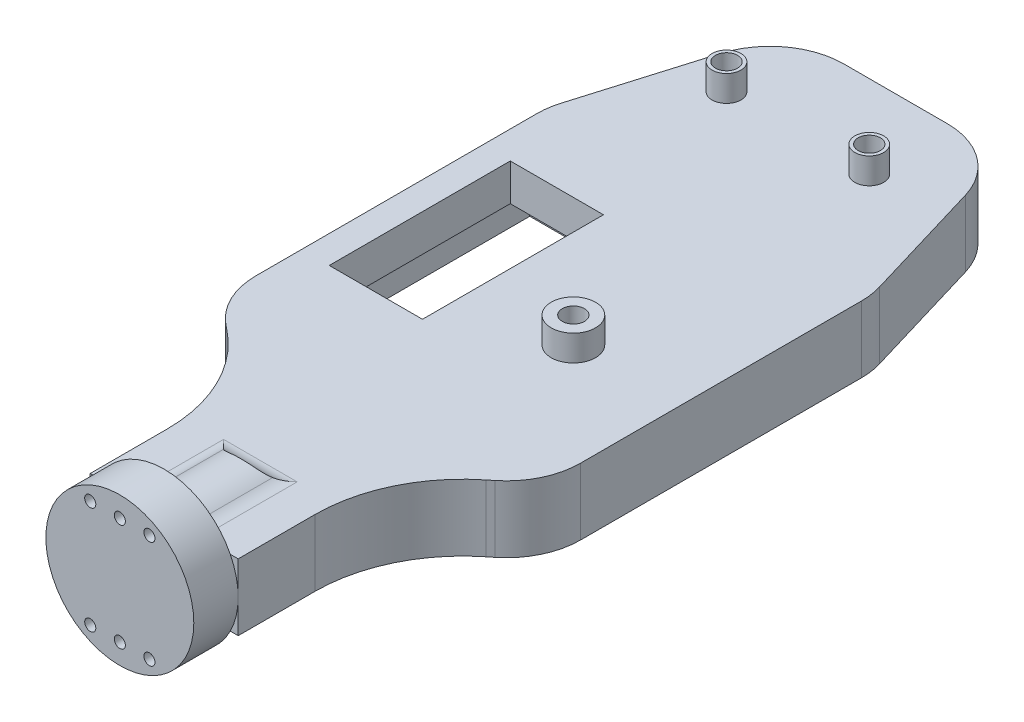
SolidWorks part; units mm, degrees
ref_plane "Front Plane" through (0, 0, 0) normal (0, 0, 1) x (1, 0, 0)
ref_plane "Top Plane" through (0, 0, 0) normal (0, 1, 0) x (1, 0, 0)
ref_plane "Right Plane" through (0, 0, 0) normal (1, 0, 0) x (0, 0, -1)
sketch "Sketch1" plane through (0, 0, 0) normal (0, 0, 1) x (1, 0, 0)
  circle A0 centre (0, 0) radius 10
  dimension "D1" = 20
extrude "Boss-Extrude1" add sketch "Sketch1" along normal blind 6 contours A0
sketch "Sketch2" plane through (0, 0, 6) normal (0, 0, 1) x (1, 0, 0)
  line L0 (0, 0) -> (15.637, 0) construction
  circle A0 centre (0, 7.25) radius 0.75
  circle A1 centre (4, 7.25) radius 0.75
  circle A2 centre (-4, 7.25) radius 0.75
  circle A3 centre (4, -7.25) radius 0.75
  circle A4 centre (0, -7.25) radius 0.75
  circle A5 centre (-4, -7.25) radius 0.75
  point P6 (0, 0)
  dimension "D3" = 1.5
  dimension "D1" = 7.25
  dimension "D2" = 4
  dimension "D4" = 4
extrude "Cut-Extrude1" cut sketch "Sketch2" against normal blind 15
sketch "Sketch4" plane through (0, 0, 0) normal (0, 0, -1) x (-1, 0, 0)
  circle A0 centre (0, 0) radius 6
  dimension "D1" = 12
extrude "Boss-Extrude3" add sketch "Sketch4" along normal blind 10
sketch "Sketch5" plane through (0, 0, 0) normal (0, 1, 0) x (1, 0, 0)
  line L0 (6, 0) -> (-6, 0) construction
  line L1 (-10, 20) -> (10, 20)
  line L2 (-10, 20) -> (-10, 0)
  line L3 (-10, 0) -> (10, 0)
  line L4 (10, 20) -> (10, 0)
  line L5 (-10, 20) -> (10, 0) construction
  line L6 (-10, 0) -> (10, 20) construction
  line L7 (10, 0) -> (-10, 0) construction
  point P0 (0, 10)
  dimension "D1" = 20
  dimension "D2" = 20
extrude "Boss-Extrude4" add sketch "Sketch5" against normal mid plane 9
sketch "Sketch6" plane through (0, 4.5, 0) normal (0, 1, 0) x (1, 0, 0)
  line L0 (10, 20) -> (35.7632, 40.5564)
  line L1 (-10, 20) -> (-35.7632, 40.5564)
  line L2 (-35.7632, 40.5564) -> (-35.7632, 98.8831)
  line L3 (-35.7632, 98.8831) -> (35.7632, 98.8831)
  line L4 (35.7632, 98.8831) -> (35.7632, 40.5564)
  line L15 (-3.9686, 0) -> (-3.9686, 10)
  line L16 (-3.9686, 10) -> (3.9686, 10)
  line L17 (3.9686, 10) -> (3.9686, 0)
  line L18 (3.9686, 0) -> (8.9303, 0)
  line L19 (8.9303, 0) -> (10, 0)
  line L20 (10, 0) -> (10, 20)
  line L21 (10, 20) -> (-10, 20)
  line L22 (-10, 20) -> (-10, 0)
  line L23 (-10, 0) -> (-8.9303, 0)
  line L24 (-8.9303, 0) -> (-3.9686, 0)
  line L31 (10, 20) -> (-10, 20)
  point P15 (0, 98.8831)
  dimension "D1" = 0
extrude "Boss-Extrude5" add sketch "Sketch6" against normal up to surface (9 mm away) up to face at (0, -4.5, -6)
sketch "Sketch7" plane through (0, -4.5, 0) normal (0, -1, 0) x (1, 0, 0)
  line L1 (-4.3923, -33.8071) -> (-19.3923, -33.8071)
  line L2 (-4.3923, -33.8071) -> (-4.3923, -68.8071)
  line L3 (-4.3923, -68.8071) -> (-19.3923, -68.8071)
  line L4 (-19.3923, -33.8071) -> (-19.3923, -68.8071)
  line L5 (-4.3923, -33.8071) -> (-19.3923, -68.8071) construction
  line L6 (-4.3923, -68.8071) -> (-19.3923, -33.8071) construction
  point P0 (-11.8923, -51.3071)
  dimension "D1" = 15
  dimension "D2" = 35
extrude "Cut-Extrude2" cut sketch "Sketch7" against normal blind 4
sketch "Sketch8" plane through (0, -0.5, 0) normal (0, -1, 0) x (1, 0, 0)
  line L0 (-11.8923, -33.8071) -> (-11.8923, -68.8071) construction
  line L1 (-4.3923, -33.8071) -> (-19.3923, -33.8071) construction
  line L2 (-19.3923, -68.8071) -> (-4.3923, -68.8071) construction
  line L3 (-18.1923, -55.7744) -> (-18.1923, -40.5057)
  line L4 (-18.1923, -40.5057) -> (-5.5923, -40.5057)
  line L5 (-5.5923, -40.5057) -> (-5.5923, -55.7744)
  line L6 (-18.1923, -55.7744) -> (-18.1923, -64.9741)
  line L7 (-18.1923, -64.9741) -> (-5.5923, -64.9741)
  line L8 (-5.5923, -64.9741) -> (-5.5923, -55.7744)
  point P0 (-11.8923, -40.5057)
extrude "Cut-Extrude3" cut sketch "Sketch8" against normal blind 14 contours L4 L5 L8 L7 L6 L3
sketch "Sketch10" plane through (0, -4.5, 0) normal (0, -1, 0) x (1, 0, 0)
  line L0 (-21.9398, -73.7699) -> (-14.4454, -98.8831)
  line L2 (-35.7632, -98.8831) -> (35.7632, -98.8831) construction
  line L5 (0, 0) -> (0, -94.3772) construction
  line L9 (-21.9398, -73.7699) -> (-21.9398, -29.5267)
  line L10 (-10, -20) -> (-35.7632, -40.5564) construction
  line L11 (-21.9398, -29.5267) -> (-35.7632, -40.5564)
  line L15 (-35.7632, -40.5564) -> (-35.7632, -98.8831)
  line L16 (-35.7632, -98.8831) -> (-14.4454, -98.8831)
  line L17 (35.7632, -40.5564) -> (35.7632, -98.8831)
  line L18 (21.9398, -29.5267) -> (35.7632, -40.5564)
  line L19 (21.9398, -73.7699) -> (21.9398, -29.5267)
  line L20 (21.9398, -73.7699) -> (14.4454, -98.8831)
  line L21 (35.7632, -98.8831) -> (14.4454, -98.8831)
extrude "Cut-Extrude4" cut sketch "Sketch10" against normal blind 10
sketch "Sketch11" plane through (0, 4.5, 0) normal (0, 1, 0) x (1, 0, 0)
  line L0 (-21.9398, 29.5267) -> (-21.9398, 73.7699) construction
  line L1 (14.4454, 98.8831) -> (-14.4454, 98.8831) construction
  line L2 (-11.6898, 87.7031) -> (7.6102, 87.7031) construction
  circle A0 centre (-11.6898, 87.7031) radius 1.95
  circle A2 centre (7.6102, 87.7031) radius 1.95
  circle A4 centre (-11.6898, 87.7031) radius 1.5
  circle A5 centre (7.6102, 87.7031) radius 1.5
  dimension "D1" = 3.9
  dimension "D6" = 3
  dimension "D5" = 3
  dimension "D2" = 10.25
  dimension "D3" = 11.18
  dimension "D4" = 19.3
extrude "Boss-Extrude6" add sketch "Sketch11" along normal blind 3.5 contours A0 | A2 region at (-13.5846, 4.5, -87.7031) region at (5.7154, 4.5, -87.7031)
sketch "Sketch12" plane through (0, 4.5, 0) normal (0, 1, 0) x (1, 0, 0)
  line L0 (7.6102, 87.7031) -> (7.6102, 47.7031) construction
  circle A0 centre (7.6102, 47.7031) radius 3
  dimension "D2" = 6
  dimension "D1" = 40
extrude "Boss-Extrude7" add sketch "Sketch12" along normal blind 3.5
sketch "Sketch13" plane through (0, 8, 0) normal (0, 1, 0) x (1, 0, 0)
  circle A0 centre (7.6102, 47.7031) radius 1.5
  dimension "D1" = 3
extrude "Cut-Extrude5" cut sketch "Sketch13" against normal blind 25
fillet "Fillet1" radius 20 2 edges at (-10, 0, -20) (10, 0, -20)
fillet "Fillet2" radius 10 6 edges at (-21.9398, 0, -29.5267) (-21.9398, 0, -73.7699) (-14.4454, 0, -98.8831) (14.4454, 0, -98.8831) (21.9398, 0, -73.7699) (21.9398, 0, -29.5267)
fillet "Fillet3" radius 3 2 edges at (0, -4.5, -10) (0, 4.5, -10)
fillet "Fillet4" radius 3 1 edges at (3.9686, 4.5, -6.5)
fillet "Fillet5" radius 3 1 edges at (-3.9686, 4.5, -6.5)
fillet "Fillet6" radius 3 2 edges at (-3.9686, -4.5, -6.5) (3.9686, -4.5, -6.5)
